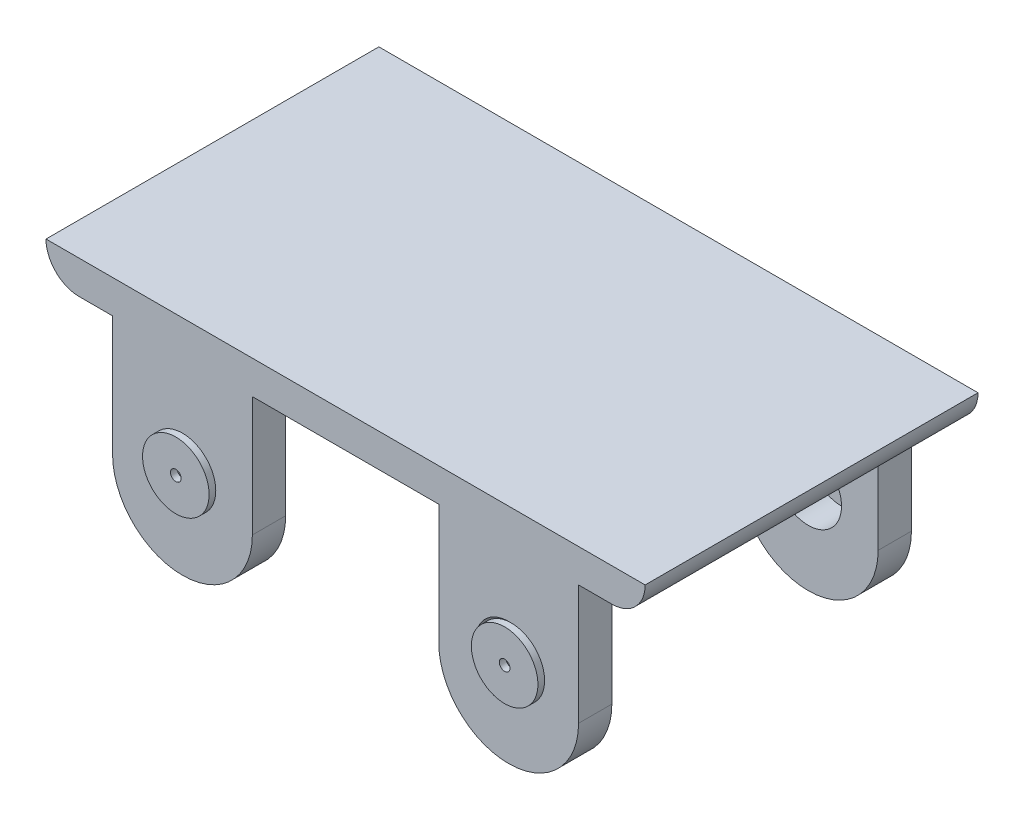
SolidWorks part; units mm, degrees
ref_plane "Front Plane" through (0, 0, 0) normal (0, 0, 1) x (1, 0, 0)
ref_plane "Top Plane" through (0, 0, 0) normal (0, 1, 0) x (1, 0, 0)
ref_plane "Right Plane" through (0, 0, 0) normal (1, 0, 0) x (0, 0, -1)
sketch "Sketch1" plane through (0, 0, 0) normal (0, 1, 0) x (1, 0, 0)
  line L1 (0, 0) -> (90, 0)
  line L2 (0, 0) -> (0, 50)
  line L3 (0, 50) -> (90, 50)
  line L4 (90, 0) -> (90, 50)
  dimension "D1" = 50
  dimension "D2" = 90
extrude "Boss-Extrude1" add sketch "Sketch1" along normal blind 5
fillet "Fillet6" radius 5 3 edges at (90, 0, -25) (90, 2.5, -50) (90, 2.5, 0)
fillet "Fillet7" radius 5 1 edges at (0, 0, -25)
sketch "Sketch2" plane through (0, 0, 0) normal (0, 0, 1) x (1, 0, 0)
  line L0 (10, 0) -> (10, -18)
  line L1 (0, 0) -> (10, 0)
  line L2 (5, 0) -> (85, 0) construction
  line L4 (31, -18) -> (31, 0)
  line L5 (45, 5) -> (45, -25.716) construction
  line L6 (0, 5) -> (90, 5) construction
  line L7 (31, 0) -> (10, 0)
  line L12 (59, 0) -> (80, 0)
  line L13 (59, -18) -> (59, 0)
  line L14 (90, 0) -> (80, 0)
  line L15 (80, 0) -> (80, -18)
  circle A0 centre (20.5, -15) radius 5
  arc A2 (31, -18) -> (10, -18) centre (20.5, -18) cw
  arc A3 (59, -18) -> (80, -18) centre (69.5, -18) ccw
  circle A4 centre (69.5, -15) radius 5
  dimension "D3" = 15
  dimension "D1" = 18
  dimension "D2" = 21
extrude "Boss-Extrude3" add sketch "Sketch2" against normal blind 5 contours A2 L4 L7 L0 A0 | L13 A3 L15 L12 A4 | A0 | A4
sketch "Sketch7" plane through (0, 0, 0) normal (0, 0, 1) x (1, 0, 0)
  line L0 (80, 0) -> (80, -18)
  line L1 (80, 0) -> (80, -18) construction
  line L2 (80, 0) -> (59, 0)
  line L3 (59, -18) -> (59, 0) construction
  line L4 (59, 0) -> (80, 0) construction
  line L5 (59, 0) -> (59, -18)
  line L6 (31, 0) -> (31, -18)
  line L7 (31, -18) -> (31, 0) construction
  line L8 (85, 0) -> (5, 0) construction
  line L9 (31, 0) -> (10, 0)
  line L10 (10, 0) -> (10, -18)
  arc A0 (59, -18) -> (80, -18) centre (69.5, -18) ccw construction
  arc A1 (80, -18) -> (59, -18) centre (69.5, -18) cw
  arc A2 (31, -18) -> (10, -18) centre (20.5, -18) cw
extrude "Boss-Extrude4" add sketch "Sketch7" along normal blind 5 from offset 50 offset against normal yes
sketch "Sketch9" plane through (0, 0, 0) normal (0, 0, 1) x (1, 0, 0)
  line L0 (45.1979, 0) -> (80, 0) construction
  line L1 (80, 0) -> (80, -18) construction
  line L2 (80, 0) -> (85, 0) construction
  line L3 (45.1979, 0.729) -> (45.1979, -29.849) construction
  line L4 (31, 0) -> (10, 0) construction
  circle A1 centre (20.5, -15) radius 5
  circle A2 centre (69.8958, -15) radius 5
  dimension "D1" = 15
extrude "Boss-Extrude5" add sketch "Sketch9" along normal blind 1
sketch "Sketch11" plane through (0, 0, 0) normal (0, 0, 1) x (1, 0, 0)
  line L0 (45, 0) -> (10, 0) construction
  line L1 (45, 0) -> (45, -24.7531) construction
  line L2 (59, 0) -> (80, 0)
  circle A0 centre (69.5, -15) radius 5
  circle A1 centre (20.5, -15) radius 5
  dimension "D1" = 15
extrude "Cut-Extrude1" cut sketch "Sketch11" along normal blind 5 from offset 5 contours A1 | A0 offset against normal yes
ref_plane "FRONT1" through (0, 0, -50) normal (0, 0, -1) x (-1, 0, 0)
sketch "Sketch12" plane through (0, 0, -50) normal (0, 0, 1) x (1, 0, 0)
  line L0 (45, 0) -> (10, 0) construction
  line L1 (45, 0) -> (45, -39.4627) construction
  line L2 (80, 0) -> (59, 0)
  circle A0 centre (69.5, -15) radius 5
  circle A1 centre (20.5, -15) radius 5
  dimension "D1" = 15
extrude "Boss-Extrude7" add sketch "Sketch12" against normal blind 1 contours A1 | A0
sketch "Sketch14" plane through (0, 0, -50) normal (0, 0, -1) x (-1, 0, 0)
  line L0 (-45, 0) -> (-80, 0) construction
  line L1 (-45, 0) -> (-45, -34.7024) construction
  line L2 (-10, 0) -> (-31, 0)
  circle A0 centre (-20.5, -15) radius 5
  circle A1 centre (-69.5, -15) radius 5
  dimension "D1" = 15
extrude "Cut-Extrude2" cut sketch "Sketch14" along normal blind 5 from offset 5 contours A1 | A0 offset against normal yes
sketch "Sketch16" plane through (0, 0, -50) normal (0, 0, -1) x (-1, 0, 0)
  line L0 (-45, 0) -> (-45, -34.3726) construction
  line L1 (-59, 0) -> (-31, 0) construction
  circle A0 centre (-69.5, -15) radius 0.8
  circle A1 centre (-20.5, -15) radius 0.8
extrude "Cut-Extrude6" cut sketch "Sketch16" along normal blind 5
sketch "Sketch17" plane through (0, 0, 0) normal (0, 0, 1) x (1, 0, 0)
  circle A0 centre (20.5, -15) radius 0.8
  circle A1 centre (69.8958, -15) radius 0.8
extrude "Cut-Extrude8" cut sketch "Sketch17" along normal blind 5
